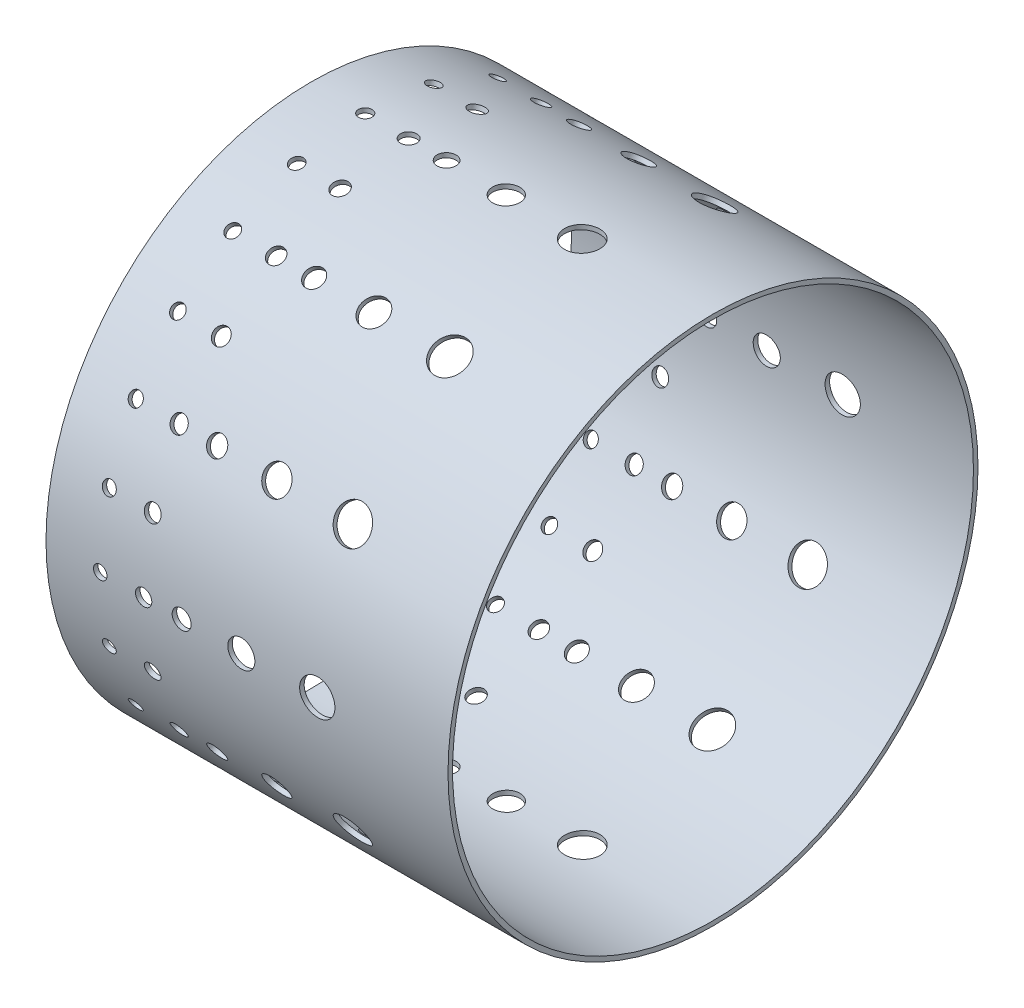
SolidWorks part; units mm, degrees
ref_plane "Front Plane" through (0, 0, 0) normal (0, 0, 1) x (1, 0, 0)
ref_plane "Top Plane" through (0, 0, 0) normal (0, 1, 0) x (1, 0, 0)
ref_plane "Right Plane" through (0, 0, 0) normal (1, 0, 0) x (0, 0, -1)
sketch "Sketch1" plane through (0, 0, 0) normal (1, 0, 0) x (0, 0, -1)
  circle A0 centre (0, 0) radius 48.8442
  circle A1 centre (0, 0) radius 48.006
  dimension "D1" = 0.8382
  dimension "D2" = 96.012
extrude "Boss-Extrude1" add sketch "Sketch1" along normal blind 74.0969
sketch "Sketch3" plane through (0, 0, 0) normal (0, 1, 0) x (1, 0, 0)
  line L0 (0, 0) -> (118.8164, 0) construction
  line L1 (0, 48.8442) -> (0, -48.8442) construction
sketch "Sketch2" plane through (0, 0, 0) normal (0, 1, 0) x (1, 0, 0)
  line L0 (0, 0) -> (89.7894, 0) construction
  line L1 (0, 48.8442) -> (0, -48.8442) construction
  circle A0 centre (10, 0) radius 1.25
  dimension "D2" = 2.5
  dimension "D1" = 10
extrude "Cut-Extrude1" cut sketch "Sketch2" against normal through all
pattern_circular "CirPattern1" count 24 over 360 about axis through (0, 0, 0) along (1, 0, 0) of "Cut-Extrude1"
sketch "Sketch4" plane through (0, 0, 0) normal (0, 0, 1) x (1, 0, 0)
  line L0 (0, 0) -> (118.8164, 0) construction
  circle A0 centre (18, 0) radius 1.5
  dimension "D1" = 18
  dimension "D2" = 3
extrude "Cut-Extrude2" cut sketch "Sketch4" against normal through all
pattern_circular "CirPattern2" count 24 over 360 about axis through (0, 0, 0) along (1, 0, 0) of "Cut-Extrude2" reverse direction yes
sketch "Sketch5" plane through (0, 0, 0) normal (0, 0, 1) x (1, 0, 0)
  line L0 (0, 0) -> (118.8164, 0) construction
  line L1 (0, 48.8442) -> (0, -48.8442) construction
  circle A0 centre (25, 0) radius 1.75
  dimension "D2" = 3.5
  dimension "D1" = 25
extrude "Cut-Extrude3" cut sketch "Sketch5" against normal through all
pattern_circular "CirPattern3" count 12 over 360 about axis through (0, 0, 0) along (1, 0, 0) of "Cut-Extrude3"
sketch "Sketch6" plane through (0, 0, 0) normal (0, 0, 1) x (1, 0, 0)
  line L0 (0, 0) -> (118.8164, 0) construction
  line L1 (0, 48.8442) -> (0, -48.8442) construction
  circle A0 centre (36, 0) radius 2.5
  dimension "D2" = 5
  dimension "D1" = 36
extrude "Cut-Extrude4" cut sketch "Sketch6" against normal through all
pattern_circular "CirPattern4" count 12 over 360 about axis through (0, 0, 0) along (1, 0, 0) of "Cut-Extrude4"
sketch "Sketch7" plane through (0, 0, 0) normal (0, 1, 0) x (1, 0, 0)
  line L0 (0, 0) -> (118.8164, 0) construction
  circle A0 centre (50, 0) radius 3.25
  dimension "D1" = 50
  dimension "D2" = 6.5
extrude "Cut-Extrude5" cut sketch "Sketch7" against normal through all
pattern_circular "CirPattern5" count 12 over 360 about axis through (74.0969, 0, 0) along (-1, 0, 0) of "Cut-Extrude5"
